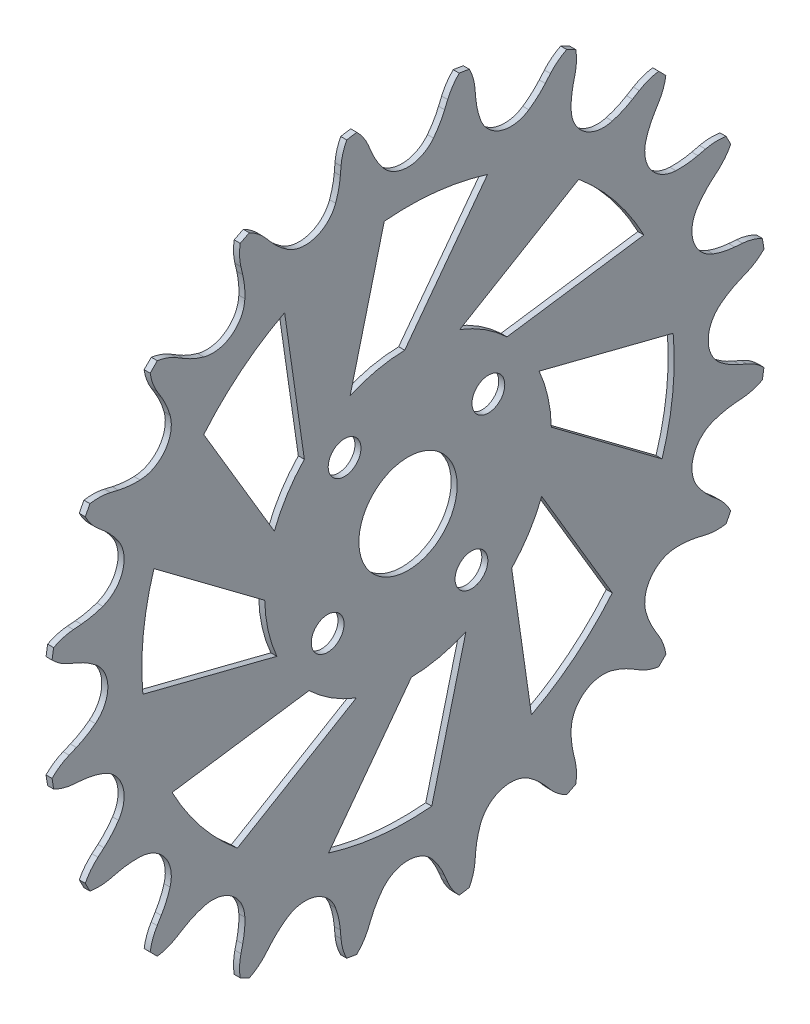
SolidWorks part; units mm, degrees
ref_plane "Front Plane" through (0, 0, 0) normal (0, 0, 1) x (1, 0, 0)
ref_plane "Top Plane" through (0, 0, 0) normal (0, 1, 0) x (1, 0, 0)
ref_plane "Right Plane" through (0, 0, 0) normal (1, 0, 0) x (0, 0, -1)
sketch "Sketch1" plane through (0, 0, 0) normal (1, 0, 0) x (0, 0, -1)
  circle A0 centre (0, 0) radius 119.2941
  circle A1 centre (0, 0) radius 6
  dimension "D1" = 12
base flange "Base-Flange1" sketch "Sketch1" thickness 0.7366 reverse thickness direction no parameters "D1"=0.7366
extrude "Cut-Extrude1" cut sketch "Sketch2" against normal through all
sketch "Sketch2" plane through (42.1838, -5.8334, -4.0708) normal (1, 0, 0) x (0, 0, -1)
  line L6 (-12.2506, 46.677) -> (-12.3314, 45.7151)
  line L7 (-8.5387, 46.3158) -> (-8.9127, 47.2057)
  line L12 (0.7711, 47.2057) -> (0.3971, 46.3158)
  line L13 (4.1898, 45.7151) -> (4.109, 46.677)
  line L16 (13.3189, 43.6846) -> (12.6882, 42.9538)
  line L17 (16.1096, 41.2105) -> (16.33, 42.1503)
  line L24 (24.1644, 36.4583) -> (23.3388, 35.9582)
  line L25 (26.054, 33.243) -> (26.5541, 34.0686)
  line L30 (32.2461, 26.2342) -> (31.3063, 26.0138)
  line L31 (33.0496, 22.5924) -> (33.7804, 23.2231)
  line L36 (36.7728, 14.0132) -> (35.8109, 14.094)
  line L37 (36.4116, 10.3013) -> (37.3015, 10.6753)
  line L42 (37.3015, 0.9915) -> (36.4116, 1.3655)
  line L43 (35.8109, -2.4272) -> (36.7728, -2.3464)
  line L48 (33.7804, -11.5563) -> (33.0496, -10.9255)
  line L49 (31.3063, -14.347) -> (32.2461, -14.5674)
  line L54 (26.5541, -22.4018) -> (26.054, -21.5761)
  line L55 (23.3388, -24.2914) -> (24.1644, -24.7915)
  line L60 (16.33, -30.4835) -> (16.1096, -29.5437)
  line L61 (12.6882, -31.287) -> (13.3189, -32.0177)
  line L66 (4.109, -35.0102) -> (4.1898, -34.0483)
  line L67 (0.3971, -34.649) -> (0.7711, -35.5389)
  line L72 (-8.9127, -35.5389) -> (-8.5387, -34.649)
  line L73 (-12.3314, -34.0483) -> (-12.2506, -35.0102)
  line L78 (-21.4605, -32.0177) -> (-20.8297, -31.287)
  line L79 (-24.2512, -29.5437) -> (-24.4716, -30.4835)
  line L84 (-32.306, -24.7915) -> (-31.4803, -24.2914)
  line L85 (-34.1956, -21.5761) -> (-34.6957, -22.4018)
  line L90 (-40.3877, -14.5674) -> (-39.4479, -14.347)
  line L91 (-41.1912, -10.9255) -> (-41.9219, -11.5563)
  line L96 (-44.9144, -2.3464) -> (-43.9525, -2.4272)
  line L97 (-44.5532, 1.3655) -> (-45.4431, 0.9915)
  line L102 (-45.4431, 10.6753) -> (-44.5532, 10.3013)
  line L103 (-43.9525, 14.094) -> (-44.9144, 14.0132)
  line L108 (-41.9219, 23.2231) -> (-41.1912, 22.5924)
  line L109 (-39.4479, 26.0138) -> (-40.3877, 26.2342)
  line L114 (-34.6957, 34.0686) -> (-34.1956, 33.243)
  line L115 (-31.4803, 35.9582) -> (-32.306, 36.4583)
  line L120 (-24.4716, 42.1503) -> (-24.2512, 41.2105)
  line L121 (-20.8297, 42.9538) -> (-21.4605, 43.6846)
  arc A11 (-6.4862, 43.308) -> (-1.6554, 43.308) centre (-4.0708, 46.4255) ccw
  arc A13 (16.0021, 37.5707) -> (19.9103, 34.7312) centre (19.7886, 38.6731) ccw
  arc A24 (-11.552, 49.0936) -> (-12.2506, 46.677) centre (-5.867, 46.141) ccw
  arc A25 (-12.9085, 43.0899) -> (-12.3314, 45.7151) centre (-22.4574, 46.5654) ccw
  arc A26 (-13.3539, 42.2202) -> (-12.9085, 43.0899) centre (-16.6144, 44.4388) ccw
  arc A27 (-6.4862, 43.308) -> (-13.3539, 42.2202) centre (-4.0708, 5.8334) ccw
  arc A28 (-7.1785, 43.9975) -> (-6.4862, 43.308) centre (-4.0708, 46.4255) ccw
  arc A29 (-8.5387, 46.3158) -> (-7.1785, 43.9975) centre (0.829, 50.2536) ccw
  arc A30 (-8.9127, 47.2057) -> (-10.3239, 49.2881) centre (-14.8182, 44.7233) ccw
  arc A31 (-10.3239, 49.2881) -> (-11.552, 49.0936) centre (-4.0708, 5.8334) ccw
  arc A38 (5.2123, 42.2202) -> (9.8067, 40.7274) centre (8.4729, 44.4388) ccw
  arc A51 (4.109, 46.677) -> (3.4104, 49.0936) centre (-2.2745, 46.141) ccw
  arc A52 (3.4104, 49.0936) -> (2.1823, 49.2881) centre (-4.0708, 5.8334) ccw
  arc A53 (2.1823, 49.2881) -> (0.7711, 47.2057) centre (6.6766, 44.7233) ccw
  arc A54 (-0.9631, 43.9975) -> (0.3971, 46.3158) centre (-8.9706, 50.2536) ccw
  arc A55 (-1.6554, 43.308) -> (-0.9631, 43.9975) centre (-4.0708, 46.4255) ccw
  arc A56 (5.2123, 42.2202) -> (-1.6554, 43.308) centre (-4.0708, 5.8334) ccw
  arc A57 (4.767, 43.0899) -> (5.2123, 42.2202) centre (8.4729, 44.4388) ccw
  arc A58 (4.1898, 45.7151) -> (4.767, 43.0899) centre (14.3158, 46.5654) ccw
  arc A68 (16.33, 42.1503) -> (16.4124, 44.6645) centre (10.0933, 43.6131) ccw
  arc A69 (16.4124, 44.6645) -> (15.3045, 45.229) centre (-4.0708, 5.8334) ccw
  arc A70 (15.3045, 45.229) -> (13.3189, 43.6846) centre (18.1682, 39.4987) ccw
  arc A71 (10.6782, 41.1693) -> (12.6882, 42.9538) centre (4.9958, 49.5937) ccw
  arc A72 (9.8067, 40.7274) -> (10.6782, 41.1693) centre (8.4729, 44.4388) ccw
  arc A73 (16.0021, 37.5707) -> (9.8067, 40.7274) centre (-4.0708, 5.8334) ccw
  arc A74 (15.8473, 38.5355) -> (16.0021, 37.5707) centre (19.7886, 38.6731) ccw
  arc A75 (16.1096, 41.2105) -> (15.8473, 38.5355) centre (26.0028, 38.8901) ccw
  arc A90 (24.827, 29.8145) -> (27.6665, 25.9063) centre (28.7689, 29.6928) ccw
  arc A103 (26.5541, 34.0686) -> (27.4094, 36.4343) centre (21.0746, 37.3871) ccw
  arc A104 (27.4094, 36.4343) -> (26.5301, 37.3136) centre (-4.0708, 5.8334) ccw
  arc A105 (26.5301, 37.3136) -> (24.1644, 36.4583) centre (27.4829, 30.9788) ccw
  arc A106 (20.8757, 34.8821) -> (23.3388, 35.9582) centre (18.0747, 44.6501) ccw
  arc A107 (19.9103, 34.7312) -> (20.8757, 34.8821) centre (19.7886, 38.6731) ccw
  arc A108 (24.827, 29.8145) -> (19.9103, 34.7312) centre (-4.0708, 5.8334) ccw
  arc A109 (24.9779, 30.7799) -> (24.827, 29.8145) centre (28.7689, 29.6928) ccw
  arc A110 (26.054, 33.243) -> (24.9779, 30.7799) centre (34.7459, 27.9789) ccw
  arc A117 (30.8232, 19.7109) -> (32.316, 15.1165) centre (34.5346, 18.3771) ccw
  arc A130 (33.7804, 23.2231) -> (35.3248, 25.2087) centre (29.5945, 28.0724) ccw
  arc A131 (35.3248, 25.2087) -> (34.7603, 26.3166) centre (-4.0708, 5.8334) ccw
  arc A132 (34.7603, 26.3166) -> (32.2461, 26.2342) centre (33.7089, 19.9975) ccw
  arc A133 (28.6313, 25.7515) -> (31.3063, 26.0138) centre (28.9859, 35.907) ccw
  arc A134 (27.6665, 25.9063) -> (28.6313, 25.7515) centre (28.7689, 29.6928) ccw
  arc A135 (30.8232, 19.7109) -> (27.6665, 25.9063) centre (-4.0708, 5.8334) ccw
  arc A136 (31.2651, 20.5824) -> (30.8232, 19.7109) centre (34.5346, 18.3771) ccw
  arc A137 (33.0496, 22.5924) -> (31.2651, 20.5824) centre (39.6895, 14.9) ccw
  arc A144 (33.4038, 8.2488) -> (33.4038, 3.418) centre (36.5213, 5.8334) ccw
  arc A157 (37.3015, 10.6753) -> (39.3839, 12.0865) centre (34.8191, 16.5808) ccw
  arc A158 (39.3839, 12.0865) -> (39.1894, 13.3146) centre (-4.0708, 5.8334) ccw
  arc A159 (39.1894, 13.3146) -> (36.7728, 14.0132) centre (36.2368, 7.6297) ccw
  arc A160 (33.1857, 14.6712) -> (35.8109, 14.094) centre (36.6612, 24.22) ccw
  arc A161 (32.316, 15.1165) -> (33.1857, 14.6712) centre (34.5346, 18.3771) ccw
  arc A162 (33.4038, 8.2488) -> (32.316, 15.1165) centre (-4.0708, 5.8334) ccw
  arc A163 (34.0933, 8.9411) -> (33.4038, 8.2488) centre (36.5213, 5.8334) ccw
  arc A164 (36.4116, 10.3013) -> (34.0933, 8.9411) centre (40.3494, 0.9336) ccw
  arc A171 (32.316, -3.4497) -> (30.8232, -8.044) centre (34.5346, -6.7102) ccw
  arc A184 (36.7728, -2.3464) -> (39.1894, -1.6478) centre (36.2368, 4.0372) ccw
  arc A185 (39.1894, -1.6478) -> (39.3839, -0.4197) centre (-4.0708, 5.8334) ccw
  arc A186 (39.3839, -0.4197) -> (37.3015, 0.9915) centre (34.8191, -4.914) ccw
  arc A187 (34.0933, 2.7257) -> (36.4116, 1.3655) centre (40.3494, 10.7332) ccw
  arc A188 (33.4038, 3.418) -> (34.0933, 2.7257) centre (36.5213, 5.8334) ccw
  arc A189 (32.316, -3.4497) -> (33.4038, 3.418) centre (-4.0708, 5.8334) ccw
  arc A190 (33.1857, -3.0043) -> (32.316, -3.4497) centre (34.5346, -6.7102) ccw
  arc A191 (35.8109, -2.4272) -> (33.1857, -3.0043) centre (36.6612, -12.5532) ccw
  arc A198 (27.6665, -14.2395) -> (24.827, -18.1477) centre (28.7689, -18.026) ccw
  arc A211 (32.2461, -14.5674) -> (34.7603, -14.6498) centre (33.7089, -8.3307) ccw
  arc A212 (34.7603, -14.6498) -> (35.3248, -13.5419) centre (-4.0708, 5.8334) ccw
  arc A213 (35.3248, -13.5419) -> (33.7804, -11.5563) centre (29.5945, -16.4056) ccw
  arc A214 (31.2651, -8.9155) -> (33.0496, -10.9255) centre (39.6895, -3.2332) ccw
  arc A215 (30.8232, -8.044) -> (31.2651, -8.9155) centre (34.5346, -6.7102) ccw
  arc A216 (27.6665, -14.2395) -> (30.8232, -8.044) centre (-4.0708, 5.8334) ccw
  arc A217 (28.6313, -14.0847) -> (27.6665, -14.2395) centre (28.7689, -18.026) ccw
  arc A218 (31.3063, -14.347) -> (28.6313, -14.0847) centre (28.9859, -24.2401) ccw
  arc A225 (19.9103, -23.0644) -> (16.0021, -25.9039) centre (19.7886, -27.0063) ccw
  arc A238 (24.1644, -24.7915) -> (26.5301, -25.6467) centre (27.4829, -19.312) ccw
  arc A239 (26.5301, -25.6467) -> (27.4094, -24.7675) centre (-4.0708, 5.8334) ccw
  arc A240 (27.4094, -24.7675) -> (26.5541, -22.4018) centre (21.0746, -25.7203) ccw
  arc A241 (24.9779, -19.1131) -> (26.054, -21.5761) centre (34.7459, -16.3121) ccw
  arc A242 (24.827, -18.1477) -> (24.9779, -19.1131) centre (28.7689, -18.026) ccw
  arc A243 (19.9103, -23.0644) -> (24.827, -18.1477) centre (-4.0708, 5.8334) ccw
  arc A244 (20.8757, -23.2153) -> (19.9103, -23.0644) centre (19.7886, -27.0063) ccw
  arc A245 (23.3388, -24.2914) -> (20.8757, -23.2153) centre (18.0747, -32.9833) ccw
  arc A252 (9.8067, -29.0606) -> (5.2123, -30.5534) centre (8.4729, -32.7719) ccw
  arc A265 (13.3189, -32.0177) -> (15.3045, -33.5622) centre (18.1682, -27.8319) ccw
  arc A266 (15.3045, -33.5622) -> (16.4124, -32.9977) centre (-4.0708, 5.8334) ccw
  arc A267 (16.4124, -32.9977) -> (16.33, -30.4835) centre (10.0933, -31.9463) ccw
  arc A268 (15.8473, -26.8686) -> (16.1096, -29.5437) centre (26.0028, -27.2233) ccw
  arc A269 (16.0021, -25.9039) -> (15.8473, -26.8686) centre (19.7886, -27.0063) ccw
  arc A270 (9.8067, -29.0606) -> (16.0021, -25.9039) centre (-4.0708, 5.8334) ccw
  arc A271 (10.6782, -29.5024) -> (9.8067, -29.0606) centre (8.4729, -32.7719) ccw
  arc A272 (12.6882, -31.287) -> (10.6782, -29.5024) centre (4.9958, -37.9268) ccw
  arc A279 (-1.6554, -31.6412) -> (-6.4862, -31.6412) centre (-4.0708, -34.7587) ccw
  arc A292 (0.7711, -35.5389) -> (2.1823, -37.6213) centre (6.6766, -33.0564) ccw
  arc A293 (2.1823, -37.6213) -> (3.4104, -37.4268) centre (-4.0708, 5.8334) ccw
  arc A294 (3.4104, -37.4268) -> (4.109, -35.0102) centre (-2.2745, -34.4742) ccw
  arc A295 (4.767, -31.4231) -> (4.1898, -34.0483) centre (14.3158, -34.8986) ccw
  arc A296 (5.2123, -30.5534) -> (4.767, -31.4231) centre (8.4729, -32.7719) ccw
  arc A297 (-1.6554, -31.6412) -> (5.2123, -30.5534) centre (-4.0708, 5.8334) ccw
  arc A298 (-0.9631, -32.3307) -> (-1.6554, -31.6412) centre (-4.0708, -34.7587) ccw
  arc A299 (0.3971, -34.649) -> (-0.9631, -32.3307) centre (-8.9706, -38.5868) ccw
  arc A306 (-13.3539, -30.5534) -> (-17.9482, -29.0606) centre (-16.6144, -32.7719) ccw
  arc A319 (-12.2506, -35.0102) -> (-11.552, -37.4268) centre (-5.867, -34.4742) ccw
  arc A320 (-11.552, -37.4268) -> (-10.3239, -37.6213) centre (-4.0708, 5.8334) ccw
  arc A321 (-10.3239, -37.6213) -> (-8.9127, -35.5389) centre (-14.8182, -33.0564) ccw
  arc A322 (-7.1785, -32.3307) -> (-8.5387, -34.649) centre (0.829, -38.5868) ccw
  arc A323 (-6.4862, -31.6412) -> (-7.1785, -32.3307) centre (-4.0708, -34.7587) ccw
  arc A324 (-13.3539, -30.5534) -> (-6.4862, -31.6412) centre (-4.0708, 5.8334) ccw
  arc A325 (-12.9085, -31.4231) -> (-13.3539, -30.5534) centre (-16.6144, -32.7719) ccw
  arc A326 (-12.3314, -34.0483) -> (-12.9085, -31.4231) centre (-22.4574, -34.8986) ccw
  arc A333 (-24.1437, -25.9039) -> (-28.0519, -23.0644) centre (-27.9302, -27.0063) ccw
  arc A346 (-24.4716, -30.4835) -> (-24.554, -32.9977) centre (-18.2349, -31.9463) ccw
  arc A347 (-24.554, -32.9977) -> (-23.4461, -33.5622) centre (-4.0708, 5.8334) ccw
  arc A348 (-23.4461, -33.5622) -> (-21.4605, -32.0177) centre (-26.3098, -27.8319) ccw
  arc A349 (-18.8197, -29.5024) -> (-20.8297, -31.287) centre (-13.1374, -37.9268) ccw
  arc A350 (-17.9482, -29.0606) -> (-18.8197, -29.5024) centre (-16.6144, -32.7719) ccw
  arc A351 (-24.1437, -25.9039) -> (-17.9482, -29.0606) centre (-4.0708, 5.8334) ccw
  arc A352 (-23.9889, -26.8686) -> (-24.1437, -25.9039) centre (-27.9302, -27.0063) ccw
  arc A353 (-24.2512, -29.5437) -> (-23.9889, -26.8686) centre (-34.1443, -27.2233) ccw
  arc A360 (-32.9686, -18.1477) -> (-35.8081, -14.2395) centre (-36.9105, -18.026) ccw
  arc A373 (-34.6957, -22.4018) -> (-35.5509, -24.7675) centre (-29.2162, -25.7203) ccw
  arc A374 (-35.5509, -24.7675) -> (-34.6717, -25.6467) centre (-4.0708, 5.8334) ccw
  arc A375 (-34.6717, -25.6467) -> (-32.306, -24.7915) centre (-35.6245, -19.312) ccw
  arc A376 (-29.0173, -23.2153) -> (-31.4803, -24.2914) centre (-26.2163, -32.9833) ccw
  arc A377 (-28.0519, -23.0644) -> (-29.0173, -23.2153) centre (-27.9302, -27.0063) ccw
  arc A378 (-32.9686, -18.1477) -> (-28.0519, -23.0644) centre (-4.0708, 5.8334) ccw
  arc A379 (-33.1195, -19.1131) -> (-32.9686, -18.1477) centre (-36.9105, -18.026) ccw
  arc A380 (-34.1956, -21.5761) -> (-33.1195, -19.1131) centre (-42.8875, -16.3121) ccw
  arc A387 (-38.9648, -8.044) -> (-40.4576, -3.4497) centre (-42.6762, -6.7102) ccw
  arc A400 (-41.9219, -11.5563) -> (-43.4664, -13.5419) centre (-37.7361, -16.4056) ccw
  arc A401 (-43.4664, -13.5419) -> (-42.9019, -14.6498) centre (-4.0708, 5.8334) ccw
  arc A402 (-42.9019, -14.6498) -> (-40.3877, -14.5674) centre (-41.8505, -8.3307) ccw
  arc A403 (-36.7728, -14.0847) -> (-39.4479, -14.347) centre (-37.1275, -24.2401) ccw
  arc A404 (-35.8081, -14.2395) -> (-36.7728, -14.0847) centre (-36.9105, -18.026) ccw
  arc A405 (-38.9648, -8.044) -> (-35.8081, -14.2395) centre (-4.0708, 5.8334) ccw
  arc A406 (-39.4067, -8.9155) -> (-38.9648, -8.044) centre (-42.6762, -6.7102) ccw
  arc A407 (-41.1912, -10.9255) -> (-39.4067, -8.9155) centre (-47.831, -3.2332) ccw
  arc A414 (-41.5454, 3.418) -> (-41.5454, 8.2488) centre (-44.6629, 5.8334) ccw
  arc A427 (-45.4431, 0.9915) -> (-47.5255, -0.4197) centre (-42.9606, -4.914) ccw
  arc A428 (-47.5255, -0.4197) -> (-47.331, -1.6478) centre (-4.0708, 5.8334) ccw
  arc A429 (-47.331, -1.6478) -> (-44.9144, -2.3464) centre (-44.3784, 4.0372) ccw
  arc A430 (-41.3273, -3.0043) -> (-43.9525, -2.4272) centre (-44.8028, -12.5532) ccw
  arc A431 (-40.4576, -3.4497) -> (-41.3273, -3.0043) centre (-42.6762, -6.7102) ccw
  arc A432 (-41.5454, 3.418) -> (-40.4576, -3.4497) centre (-4.0708, 5.8334) ccw
  arc A433 (-42.2349, 2.7257) -> (-41.5454, 3.418) centre (-44.6629, 5.8334) ccw
  arc A434 (-44.5532, 1.3655) -> (-42.2349, 2.7257) centre (-48.491, 10.7332) ccw
  arc A441 (-40.4576, 15.1165) -> (-38.9648, 19.7109) centre (-42.6762, 18.3771) ccw
  arc A454 (-44.9144, 14.0132) -> (-47.331, 13.3146) centre (-44.3784, 7.6297) ccw
  arc A455 (-47.331, 13.3146) -> (-47.5255, 12.0865) centre (-4.0708, 5.8334) ccw
  arc A456 (-47.5255, 12.0865) -> (-45.4431, 10.6753) centre (-42.9606, 16.5808) ccw
  arc A457 (-42.2349, 8.9411) -> (-44.5532, 10.3013) centre (-48.491, 0.9336) ccw
  arc A458 (-41.5454, 8.2488) -> (-42.2349, 8.9411) centre (-44.6629, 5.8334) ccw
  arc A459 (-40.4576, 15.1165) -> (-41.5454, 8.2488) centre (-4.0708, 5.8334) ccw
  arc A460 (-41.3273, 14.6712) -> (-40.4576, 15.1165) centre (-42.6762, 18.3771) ccw
  arc A461 (-43.9525, 14.094) -> (-41.3273, 14.6712) centre (-44.8028, 24.22) ccw
  arc A468 (-35.8081, 25.9063) -> (-32.9686, 29.8145) centre (-36.9105, 29.6928) ccw
  arc A481 (-40.3877, 26.2342) -> (-42.9019, 26.3166) centre (-41.8505, 19.9975) ccw
  arc A482 (-42.9019, 26.3166) -> (-43.4664, 25.2087) centre (-4.0708, 5.8334) ccw
  arc A483 (-43.4664, 25.2087) -> (-41.9219, 23.2231) centre (-37.7361, 28.0724) ccw
  arc A484 (-39.4067, 20.5824) -> (-41.1912, 22.5924) centre (-47.831, 14.9) ccw
  arc A485 (-38.9648, 19.7109) -> (-39.4067, 20.5824) centre (-42.6762, 18.3771) ccw
  arc A486 (-35.8081, 25.9063) -> (-38.9648, 19.7109) centre (-4.0708, 5.8334) ccw
  arc A487 (-36.7728, 25.7515) -> (-35.8081, 25.9063) centre (-36.9105, 29.6928) ccw
  arc A488 (-39.4479, 26.0138) -> (-36.7728, 25.7515) centre (-37.1275, 35.907) ccw
  arc A495 (-28.0519, 34.7312) -> (-24.1437, 37.5707) centre (-27.9302, 38.6731) ccw
  arc A508 (-32.306, 36.4583) -> (-34.6717, 37.3136) centre (-35.6245, 30.9788) ccw
  arc A509 (-34.6717, 37.3136) -> (-35.5509, 36.4343) centre (-4.0708, 5.8334) ccw
  arc A510 (-35.5509, 36.4343) -> (-34.6957, 34.0686) centre (-29.2162, 37.3871) ccw
  arc A511 (-33.1195, 30.7799) -> (-34.1956, 33.243) centre (-42.8875, 27.9789) ccw
  arc A512 (-32.9686, 29.8145) -> (-33.1195, 30.7799) centre (-36.9105, 29.6928) ccw
  arc A513 (-28.0519, 34.7312) -> (-32.9686, 29.8145) centre (-4.0708, 5.8334) ccw
  arc A514 (-29.0173, 34.8821) -> (-28.0519, 34.7312) centre (-27.9302, 38.6731) ccw
  arc A515 (-31.4803, 35.9582) -> (-29.0173, 34.8821) centre (-26.2163, 44.6501) ccw
  circle A520 centre (-4.0708, 5.8334) radius 162.1741
  arc A522 (-17.9482, 40.7274) -> (-13.3539, 42.2202) centre (-16.6144, 44.4388) ccw
  arc A535 (-21.4605, 43.6846) -> (-23.4461, 45.229) centre (-26.3098, 39.4987) ccw
  arc A536 (-23.4461, 45.229) -> (-24.554, 44.6645) centre (-4.0708, 5.8334) ccw
  arc A537 (-24.554, 44.6645) -> (-24.4716, 42.1503) centre (-18.2349, 43.6131) ccw
  arc A538 (-23.9889, 38.5355) -> (-24.2512, 41.2105) centre (-34.1443, 38.8901) ccw
  arc A539 (-24.1437, 37.5707) -> (-23.9889, 38.5355) centre (-27.9302, 38.6731) ccw
  arc A540 (-17.9482, 40.7274) -> (-24.1437, 37.5707) centre (-4.0708, 5.8334) ccw
  arc A541 (-18.8197, 41.1693) -> (-17.9482, 40.7274) centre (-16.6144, 44.4388) ccw
  arc A542 (-20.8297, 42.9538) -> (-18.8197, 41.1693) centre (-13.1374, 49.5937) ccw
sketch "Sketch4" plane through (0, 0, 0) normal (1, 0, 0) x (0, 0, -1)
  line L0 (-12.0852, -12.6569) -> (-32.1032, -15.5439)
  line L1 (-6.3217, -16.3183) -> (-23.7111, -26.646)
  line L2 (-16.0089, -7.0686) -> (-35.6078, -2.0753)
  line L3 (-17.4953, -0.4042) -> (-33.6915, 11.7092)
  line L4 (-16.3183, 6.3217) -> (-26.646, 23.7111)
  line L5 (-12.6569, 12.0852) -> (-15.5439, 32.1032)
  line L6 (-7.0686, 16.0089) -> (-2.0753, 35.6078)
  line L7 (-0.4042, 17.4953) -> (11.7092, 33.6915)
  line L8 (6.3217, 16.3183) -> (23.7111, 26.646)
  line L9 (12.0852, 12.6569) -> (32.1032, 15.5439)
  line L10 (16.0089, 7.0686) -> (35.6078, 2.0753)
  line L11 (17.4953, 0.4042) -> (33.6915, -11.7092)
  line L12 (16.3183, -6.3217) -> (26.646, -23.7111)
  line L13 (12.6569, -12.0852) -> (15.5439, -32.1032)
  line L14 (7.0686, -16.0089) -> (2.0753, -35.6078)
  line L15 (0.4042, -17.4953) -> (-11.7092, -33.6915)
  circle A0 centre (0, 0) radius 17.5
  circle A1 centre (0, 0) radius 32.5
  point P34 (1.9713, -1.5721)
  point P40 (0, 0)
  point P41 (0, 0)
  dimension "D2" = 35
  dimension "D3" = 65
  dimension "D1" = 16
extrude "Cut-Extrude2" cut sketch "Sketch4" against normal blind 10
extrude "Cut-Extrude5" cut sketch "Sketch7" along normal through all both normal cut yes
sketch "Sketch7" plane through (0, -41.9541, 8.1803) normal (-1, 0, 0) x (0, 0, 1)
  circle A0 centre (1.6312, 34.2091) radius 2
  circle A1 centre (-15.9252, 32.1426) radius 2
  circle A2 centre (-17.9918, 49.6991) radius 2
  circle A3 centre (-0.4353, 51.7656) radius 2
sketch "Bend-Lines1" plane through (0, 0, 0) normal (0, 1, 0) x (1, 0, 0)
sketch "Bounding-Box1" plane through (0, 0, 0) normal (0, 1, 0) x (1, 0, 0)
sheet metal parameters "Sheet-Metal1" thickness 0.7366 parameters "D1"=0.7366
flat pattern "Flat-Pattern1" [suppressed]
sketch "Bend-Lines2" plane through (0, 0, 0) normal (0, 1, 0) x (1, 0, 0)
sketch "Bounding-Box2" [suppressed] plane through (0, 0, 0) normal (0, 1, 0) x (1, 0, 0)
sheet metal parameters "Sheet-Metal9" thickness 0.7366 parameters "D1"=0.7366
flat pattern "Flat-Pattern1"
sketch "Bend-Lines2" plane through (0, 0, 0) normal (0, 1, 0) x (1, 0, 0)
sketch "Bounding-Box2" [suppressed] plane through (0, 0, 0) normal (0, 1, 0) x (1, 0, 0)
sheet metal parameters "Sheet-Metal10" thickness 0.7366 parameters "D1"=0.7366
flat pattern "Flat-Pattern1"
sketch "Bend-Lines2" plane through (0, 0, 0) normal (0, 1, 0) x (1, 0, 0)
sketch "Bounding-Box2" [suppressed] plane through (0, 0, 0) normal (0, 1, 0) x (1, 0, 0)
sheet metal parameters "Sheet-Metal11" thickness 0.7366 parameters "D1"=0.7366
flat pattern "Flat-Pattern1"
sketch "Bend-Lines2" plane through (0, 0, 0) normal (0, 1, 0) x (1, 0, 0)
sketch "Bounding-Box2" [suppressed] plane through (0, 0, 0) normal (0, 1, 0) x (1, 0, 0)
